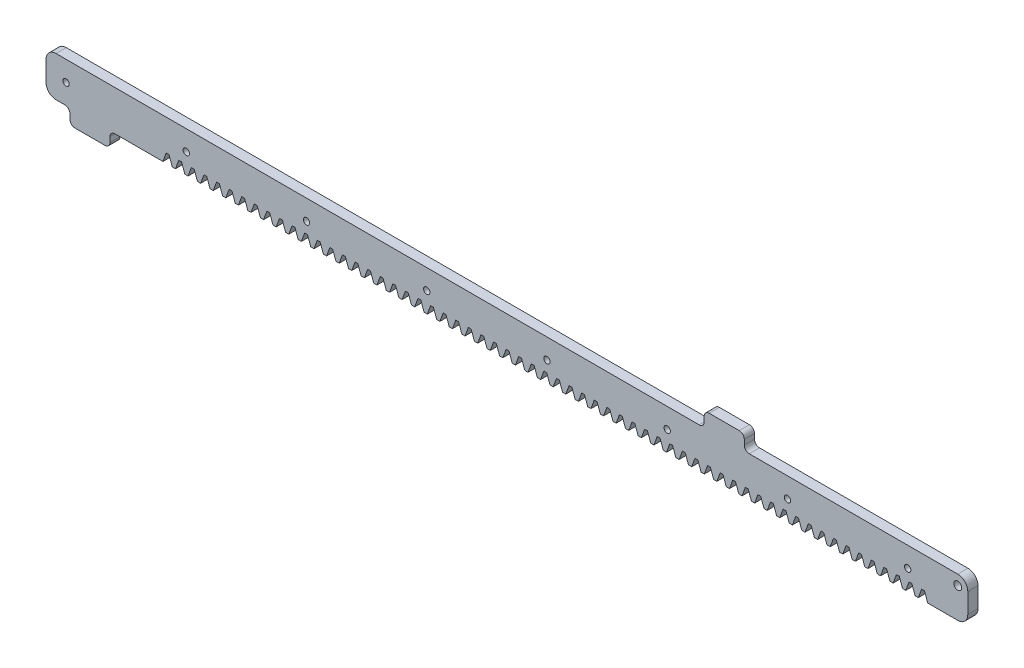
SolidWorks part; units mm, degrees
material "PC High Viscosity"
ref_plane "Front Plane" through (0, 0, 0) normal (0, 0, 1) x (1, 0, 0)
ref_plane "Top Plane" through (0, 0, 0) normal (0, 1, 0) x (1, 0, 0)
ref_plane "Right Plane" through (0, 0, 0) normal (1, 0, 0) x (0, 0, -1)
sketch "Sketch1" plane through (0, 0, 0) normal (0, 0, 1) x (1, 0, 0)
  line L1 (0, 0) -> (15.1308, 0)
  line L2 (0, 0) -> (0, 25.4)
  line L3 (0, 25.4) -> (40.5308, 25.4)
  line L4 (584.2, 0) -> (584.2, 25.4)
  line L7 (533.4, 25.4) -> (584.2, 25.4)
  line L8 (40.5308, 25.4) -> (417.1409, 25.4)
  line L9 (40.5308, 0) -> (584.2, 0)
  line L11 (584.2, 22.7162) -> (577.85, 26.3823) construction
  line L12 (577.85, 26.3823) -> (571.5, 22.7162) construction
  line L13 (571.5, 22.7162) -> (571.5, 15.3838) construction
  line L14 (571.5, 15.3838) -> (577.85, 11.7177) construction
  line L15 (577.85, 11.7177) -> (584.2, 15.3838) construction
  line L16 (584.2, 15.3838) -> (584.2, 22.7162) construction
  line L19 (590.55, 0) -> (590.55, 10.0162) construction
  line L20 (590.55, 10.0162) -> (76.2, 10.0162) construction
  line L21 (76.2, 10.0162) -> (76.2, 0) construction
  line L22 (442.5409, 25.4) -> (533.4, 25.4)
  line L26 (15.1308, 0) -> (15.1308, -9.525)
  line L27 (15.1308, -9.525) -> (40.5308, -9.525)
  line L28 (40.5308, -9.525) -> (40.5308, 0)
  line L29 (417.1409, 25.4) -> (417.1409, 34.925)
  line L30 (417.1409, 34.925) -> (442.5409, 34.925)
  line L31 (442.5409, 34.925) -> (442.5409, 25.4)
  circle A0 centre (577.85, 19.05) radius 2.4892
  circle A1 centre (577.85, 19.05) radius 6.35 construction
  dimension "D5" = 4.9784
  dimension "D6" = 40.5308
  dimension "D7" = 12.7
  dimension "D1" = 584.2
  dimension "D2" = 25.4
  dimension "D3" = 167.0591
  dimension "D4" = 9.525
  dimension "D8" = 25.4
  dimension "D9" = 25.4
extrude "Boss-Extrude1" add sketch "Sketch1" along normal blind 6.477 contours L3 | L1 L4 L3 L2 A0 | L1 region at (289.7362, 12.6919, 0)
fillet "Fillet2" radius 6.35 4 edges at (0, 0, 3.2385) (0, 25.4, 3.2385) (584.2, 25.4, 3.2385) (584.2, 0, 3.2385)
sketch "Sketch2" plane through (0, 0, 6.477) normal (0, 0, 1) x (1, 0, 0)
  line L0 (558.8, 0) -> (43.7058, 0)
  line L1 (43.7058, 0) -> (43.7058, 5.715)
  line L2 (43.7058, 5.715) -> (558.8, 5.715)
  line L3 (558.8, 5.715) -> (558.8, 0)
  line L5 (557.8755, 2.54) -> (549.711, 2.54) construction
  line L6 (558.8, 0) -> (556.7199, 5.715)
  line L7 (40.5308, 0) -> (552.8688, 0) construction
  line L8 (552.8688, 0) -> (558.8, 0)
  line L10 (556.7199, 5.715) -> (554.9488, 5.715)
  line L11 (558.8, 0) -> (552.8688, 0)
  line L12 (552.8688, 0) -> (554.9488, 5.715)
  line L13 (554.9488, 5.715) -> (556.7199, 5.715)
  line L14 (558.8, 0) -> (552.8688, 0)
  line L15 (554.9488, 5.715) -> (556.7199, 5.715)
  line L16 (558.8, 0) -> (552.8688, 0)
  line L17 (552.8688, 0) -> (558.8, 0)
  line L19 (556.7199, 5.715) -> (554.9488, 5.715) construction
  line L20 (552.8688, 0) -> (558.8, 0) construction
  line L21 (0, 0) -> (15.1308, 0) construction
  line L22 (584.2, 0) -> (584.2, 25.4) construction
  line L23 (40.5308, 0) -> (584.2, 0) construction
  point P2 (0, 0)
  point P3 (46.8808, 0)
  point P8 (553.7932, 2.54)
  point P12 (43.4302, 0)
  point P16 (557.8755, 2.54)
  point P17 (42.0933, 0)
  point P18 (43.7058, 0)
  dimension "D1" = 70
  dimension "D2" = 2.54
  dimension "D3" = 3.175
  dimension "D4" = 70
  dimension "D5" = 1.7711
  dimension "D6" = 25.4
extrude "Cut-Extrude1" cut sketch "Sketch2" against normal through all contours L12 L0 L8 L6 L2 region at (555.8344, 2.343, 6.477)
pattern_linear "LPattern1" count 61 spacing 7.9796 along (-1, 0, 0) of "Cut-Extrude1"
sketch "Sketch3" plane through (0, 0, 6.477) normal (0, 0, 1) x (1, 0, 0)
  line L2 (533.4, 25.4) -> (584.2, 25.4) construction
  line L3 (584.2, 0) -> (584.2, 25.4) construction
  circle A0 centre (546.1, 12.7) radius 2.0193
  dimension "D2" = 4.0386
  dimension "D1" = 12.7
  dimension "D3" = 38.1
extrude "Cut-Extrude2" cut sketch "Sketch3" against normal through all
pattern_linear "LPattern2" count 8 spacing 76.2 along (-1, 0, 0) of "Cut-Extrude2"
fillet "Fillet3" radius 3.175 8 edges at (417.1409, 25.4, 3.2385) (417.1409, 34.925, 3.2385) (442.5409, 34.925, 3.2385) (442.5409, 25.4, 3.2385) (40.5308, -9.525, 3.2385) (40.5308, 0, 3.2385) (15.1308, -9.525, 3.2385) (15.1308, 0, 3.2385)
